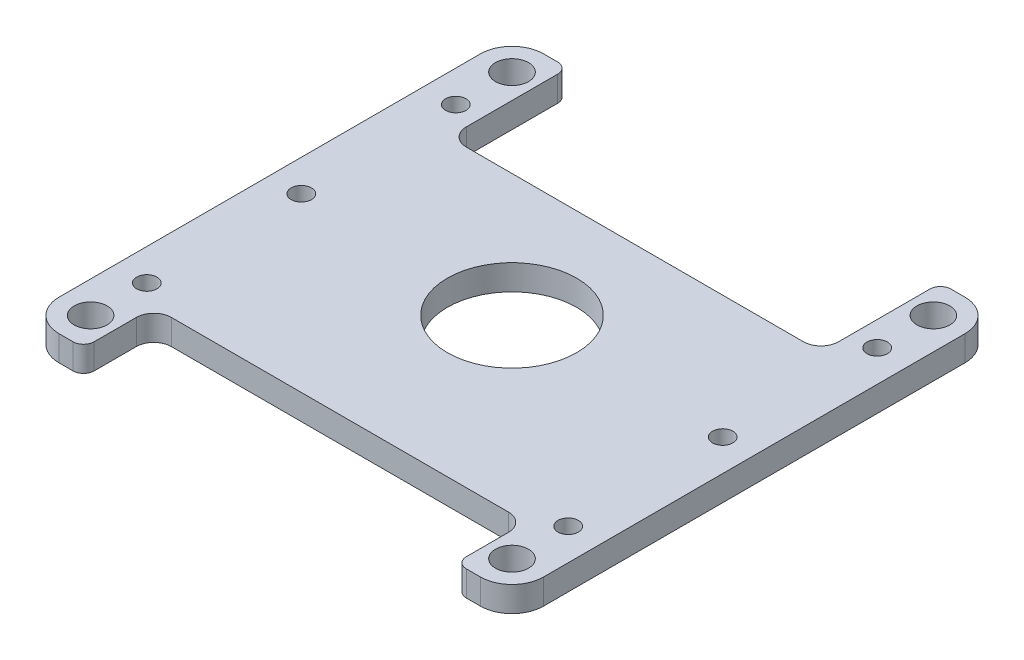
SolidWorks part; units mm, degrees
ref_plane "Front Plane" through (0, 0, 0) normal (0, 0, 1) x (1, 0, 0)
ref_plane "Top Plane" through (0, 0, 0) normal (0, 1, 0) x (1, 0, 0)
ref_plane "Right Plane" through (0, 0, 0) normal (1, 0, 0) x (0, 0, -1)
sketch "Sketch1" plane through (0, 0, 0) normal (0, 1, 0) x (1, 0, 0)
  line L1 (35, -35) -> (-35, -35)
  line L2 (35, -35) -> (35, 35)
  line L3 (35, 35) -> (-35, 35)
  line L4 (-35, -35) -> (-35, 35)
  line L5 (35, -35) -> (-35, 35) construction
  line L6 (35, 35) -> (-35, -35) construction
  point P0 (0, 0)
  dimension "D1" = 70
  dimension "D2" = 70
extrude "Boss-Extrude1" add sketch "Sketch1" along normal blind 3.6
sketch "Sketch2" plane through (0, 3.6, 0) normal (0, 1, 0) x (1, 0, 0)
  line L12 (30, 34.5) -> (28, 34.5)
  line L13 (26.5, 33) -> (26.5, 20)
  line L14 (24, 17.5) -> (-24, 17.5)
  line L15 (-26.5, 20) -> (-26.5, 33)
  line L16 (-28, 34.5) -> (-30, 34.5)
  line L17 (-34.5, 30) -> (-34.5, -30)
  line L18 (-30, -34.5) -> (-28, -34.5)
  line L19 (-26.5, -33) -> (-26.5, -27)
  line L20 (-24, -24.5) -> (24, -24.5)
  line L21 (26.5, -27) -> (26.5, -33)
  line L22 (28, -34.5) -> (30, -34.5)
  line L23 (34.5, -30) -> (34.5, 30)
  line L25 (43.8841, -42.8582) -> (-43.8841, -42.8582)
  line L26 (43.8841, -42.8582) -> (43.8841, 42.8582)
  line L27 (43.8841, 42.8582) -> (-43.8841, 42.8582)
  line L28 (-43.8841, -42.8582) -> (-43.8841, 42.8582)
  line L29 (43.8841, -42.8582) -> (-43.8841, 42.8582) construction
  line L30 (43.8841, 42.8582) -> (-43.8841, -42.8582) construction
  arc A12 (28, 34.5) -> (26.5, 33) centre (28, 33) ccw
  arc A13 (24, 17.5) -> (26.5, 20) centre (24, 20) ccw
  arc A14 (-26.5, 20) -> (-24, 17.5) centre (-24, 20) ccw
  arc A15 (-26.5, 33) -> (-28, 34.5) centre (-28, 33) ccw
  arc A16 (-30, 34.5) -> (-34.5, 30) centre (-30, 30) ccw
  arc A17 (-34.5, -30) -> (-30, -34.5) centre (-30, -30) ccw
  arc A18 (-28, -34.5) -> (-26.5, -33) centre (-28, -33) ccw
  arc A19 (-24, -24.5) -> (-26.5, -27) centre (-24, -27) ccw
  arc A20 (26.5, -27) -> (24, -24.5) centre (24, -27) ccw
  arc A21 (26.5, -33) -> (28, -34.5) centre (28, -33) ccw
  arc A22 (30, -34.5) -> (34.5, -30) centre (30, -30) ccw
  arc A23 (34.5, 30) -> (30, 34.5) centre (30, 30) ccw
  point P36 (0, 0)
  point P42 (0, 0)
  point P43 (0, 0)
  point P44 (0, 0)
  point P45 (0, 0)
  point P46 (0, 0)
  point P47 (0, 0)
  point P48 (0, 0)
  point P49 (0, 0)
  point P50 (0, 0)
  point P51 (0, 0)
  point P52 (0, 0)
  point P53 (0, 0)
  point P54 (0, 0)
  dimension "D1" = 4.5
  dimension "D2" = 42
  dimension "D4" = 2.5
  dimension "D10" = 1.5
  dimension "D3" = 69
  dimension "D5" = 2.5
  dimension "D6" = 2.5
  dimension "D7" = 13
  dimension "D8" = 48
  dimension "D9" = 60
  dimension "D11" = 8
  dimension "D12" = 8
  dimension "D13" = 10
  dimension "D14" = 17
  dimension "D15" = 8
  dimension "D16" = 8
  dimension "D17" = 17
  dimension "D18" = 10
  dimension "D19" = 34.5
  dimension "D20" = 24.5
extrude "Cut-Extrude1" cut sketch "Sketch2" against normal blind 10
sketch "Sketch4" plane through (0, 0, 0) normal (0, -1, 0) x (1, 0, 0)
  circle A0 centre (30, -30) radius 2.35 construction
  circle A1 centre (30, -22) radius 1.45 construction
  circle A2 centre (30, 0) radius 1.45 construction
  circle A3 centre (30, 22) radius 1.45 construction
  circle A4 centre (30, 30) radius 2.35 construction
  circle A5 centre (30, -30) radius 2.35
  circle A6 centre (30, -22) radius 1.45
  circle A7 centre (30, 0) radius 1.45
  circle A8 centre (30, 22) radius 1.45
  circle A9 centre (30, 30) radius 2.35
  circle A10 centre (-30, -30) radius 2.35 construction
  circle A11 centre (-30, -22) radius 1.45 construction
  circle A12 centre (0, 0) radius 9.2 construction
  circle A13 centre (-30, 0) radius 1.45 construction
  circle A14 centre (-30, 22) radius 1.45 construction
  circle A15 centre (-30, 30) radius 2.35 construction
  circle A16 centre (-30, -30) radius 2.35
  circle A17 centre (-30, -22) radius 1.45
  circle A18 centre (0, 0) radius 9.2
  circle A19 centre (-30, 0) radius 1.45
  circle A20 centre (-30, 22) radius 1.45
  circle A21 centre (-30, 30) radius 2.35
extrude "Cut-Extrude2" cut sketch "Sketch4" against normal blind 10
